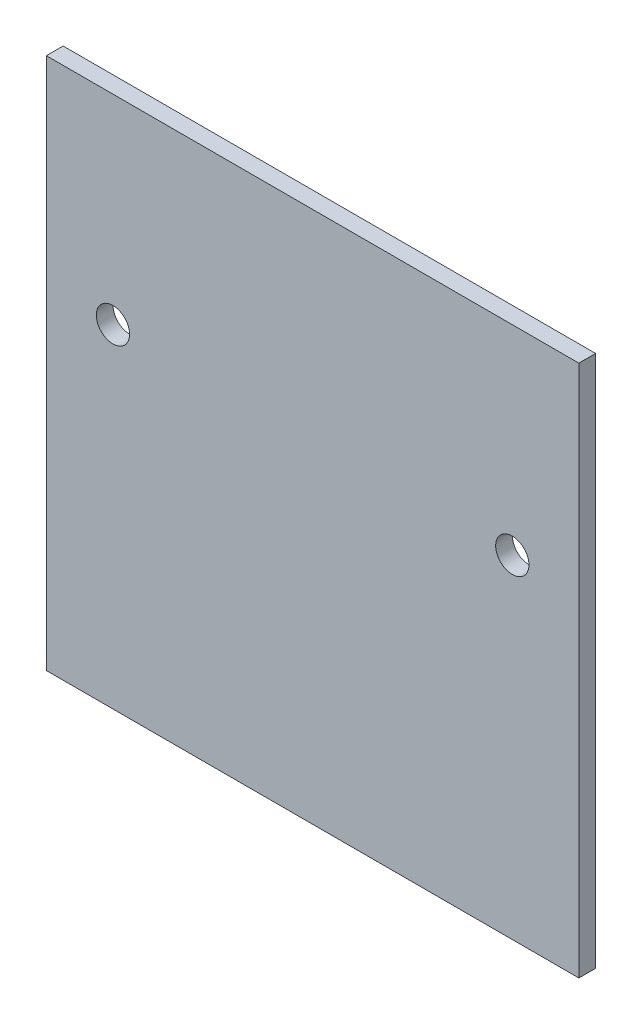
SolidWorks part; units mm, degrees
material "6061 Alloy"
ref_plane "Front Plane" through (0, 0, 0) normal (0, 0, 1) x (1, 0, 0)
ref_plane "Top Plane" through (0, 0, 0) normal (0, 1, 0) x (1, 0, 0)
ref_plane "Right Plane" through (0, 0, 0) normal (1, 0, 0) x (0, 0, -1)
sketch "Sketch2" plane through (0, 0, 0) normal (0, 0, 1) x (1, 0, 0)
  line L0 (367.9685, -43.1374) -> (375.3903, -43.1374) construction
  line L1 (339.8232, 33.108) -> (339.8232, -119.3829) construction
  line L3 (365.2232, -43.1374) -> (365.2232, -17.7374) construction
  line L4 (365.2232, -17.7374) -> (339.8232, -17.7374)
  line L5 (365.2232, -17.7374) -> (365.2232, -68.5374)
  line L6 (314.4232, -17.7374) -> (339.8232, -17.7374)
  line L7 (314.4232, -17.7374) -> (314.4232, -68.5374)
  line L8 (365.2232, -68.5374) -> (339.8237, -68.5374)
  line L9 (314.4232, -68.5374) -> (339.8237, -68.5374)
  line L10 (390.6232, 33.108) -> (289.0232, 33.108)
  line L11 (289.0232, 33.108) -> (289.0232, -119.3829)
  line L12 (289.0232, -119.3829) -> (390.6232, -119.3829)
  line L13 (390.6232, 33.108) -> (390.6232, -119.3829)
  line L14 (289.0232, -43.1374) -> (302.835, -43.1374) construction
  line L15 (302.835, -43.1374) -> (302.835, -32.805) construction
  line L16 (302.835, -32.805) -> (367.9685, -5.8258) construction
  line L17 (367.9685, -5.8258) -> (367.9685, -43.1374) construction
  line L18 (368.6791, -6.2758) -> (368.6791, -5.8258) construction
  circle A0 centre (302.835, -32.805) radius 0.45
  circle A1 centre (367.9685, -5.8258) radius 0.45
  circle A2 centre (302.835, -53.4699) radius 0.45
  circle A3 centre (375.3903, -43.1374) radius 0.45
  circle A4 centre (367.9685, -80.449) radius 0.45
  point P28 (314.4232, -43.1374)
  dimension "D1" = 50.8
  dimension "D2" = 50.8
  dimension "D3" = 50.8
  dimension "D4" = 50.8
  dimension "D5" = 13.8118
  dimension "D6" = 50.8
  dimension "D7" = 0
  dimension "D8" = 50.8
extrude "Boss-Extrude1" add sketch "Sketch2" along normal blind 3.2
sketch "Sketch3" plane through (0, 0, 3.2) normal (0, 0, 1) x (1, 0, 0)
  line L0 (339.8232, 33.108) -> (339.8232, -119.3829) construction
  line L1 (390.6232, 33.108) -> (289.0232, 33.108) construction
  line L2 (289.0232, -119.3829) -> (390.6232, -119.3829) construction
  line L3 (289.0232, -43.1374) -> (390.6232, -43.1374) construction
  line L4 (289.0232, 33.108) -> (289.0232, -119.3829) construction
  line L5 (390.6232, -119.3829) -> (390.6232, 33.108) construction
  line L6 (390.6232, 33.108) -> (377.9232, 33.108) construction
  line L7 (377.9232, 33.108) -> (377.9232, 20.408) construction
  circle A0 centre (377.9232, 20.408) radius 3.175
  circle A1 centre (301.7232, 20.408) radius 3.175
  circle A2 centre (301.7232, -106.6829) radius 3.175
  circle A3 centre (377.9232, -106.6829) radius 3.175
  dimension "D1" = 12.7
  dimension "D2" = 12.7
extrude "Cut-Extrude1" cut sketch "Sketch3" against normal blind 10
sketch "Sketch4" [suppressed] plane through (0, 0, 3.2) normal (0, 0, 1) x (1, 0, 0)
  line L0 (314.4232, -17.7374) -> (314.4232, -68.5374)
  line L1 (314.4232, -17.7374) -> (314.4232, -68.5374) construction
  line L2 (314.4232, -17.7374) -> (365.2232, -17.7374)
  line L3 (365.2232, -17.7374) -> (365.2232, -68.5374)
  line L4 (365.2232, -68.5374) -> (314.4232, -68.5374)
extrude "Boss-Extrude2" [suppressed] add sketch "Sketch4" against normal up to surface (3.2 mm away) up to face at (374.7482, -106.6829, 0)
sketch "Sketch5" plane through (0, 0, 3.2) normal (0, 0, 1) x (1, 0, 0)
  line L0 (289.0232, -43.1374) -> (390.6232, -43.1374) construction
  line L1 (289.0232, 33.108) -> (289.0232, -119.3829) construction
  line L2 (390.6232, -119.3829) -> (390.6232, 33.108) construction
  line L3 (390.6232, -43.1374) -> (390.6232, 7.6626)
  line L4 (390.6232, 7.6626) -> (289.0232, 7.6626)
  line L5 (289.0232, 7.6626) -> (289.0232, -43.1374)
  line L6 (289.0232, -43.1374) -> (289.0232, -93.9374)
  line L7 (289.0232, -93.9374) -> (390.6232, -93.9374)
  line L8 (390.6232, -93.9374) -> (390.6232, -43.1374)
  dimension "D1" = 50.8
  dimension "D2" = 50.8
extrude "Cut-Extrude3" cut sketch "Sketch5" against normal through all flip side to cut
sketch "Sketch6" plane through (0, 0, 3.2) normal (0, 0, 1) x (1, 0, 0)
  line L0 (298.5822, 7.6626) -> (298.5822, -87.2182)
  line L1 (298.5822, -87.2182) -> (383.0381, -87.2182)
  line L2 (383.0381, -87.2182) -> (383.0381, 7.6626)
  line L3 (383.0381, 7.6626) -> (298.5822, 7.6626)
  line L4 (390.6232, 7.6626) -> (289.0232, 7.6626) construction
extrude "Boss-Extrude3" add sketch "Sketch6" against normal up to surface (3.2 mm away) up to face at (339.8232, -43.1374, 0)
sketch "Sketch7" plane through (0, 0, 3.2) normal (0, 0, 1) x (1, 0, 0)
  line L0 (298.5482, -30.4374) -> (301.7232, -30.4374) construction
  line L2 (339.8232, 7.6626) -> (339.8232, -93.9374) construction
  line L3 (390.6232, 7.6626) -> (289.0232, 7.6626) construction
  line L4 (289.0232, -93.9374) -> (390.6232, -93.9374) construction
  circle A0 centre (301.7232, -30.4374) radius 3.175
  circle A1 centre (377.9232, -30.4374) radius 3.175
  dimension "D1" = 38.1
extrude "Cut-Extrude4" cut sketch "Sketch7" against normal blind 10
sketch "Sketch8" [suppressed] plane through (0, 0, 3.2) normal (0, 0, 1) x (1, 0, 0)
  line L0 (295.4324, 2.9788) -> (295.4324, -85.513)
  line L1 (295.4324, -85.513) -> (384.8396, -85.513)
  line L2 (384.8396, -85.513) -> (384.8396, 2.9788)
  line L3 (384.8396, 2.9788) -> (295.4324, 2.9788)
extrude "Boss-Extrude4" [suppressed] add sketch "Sketch8" against normal up to surface (3.2 mm away) up to face at (374.7482, -30.4374, 0)
sketch "Sketch9" [suppressed] plane through (0, 0, 3.2) normal (0, 0, 1) x (1, 0, 0)
  line L2 (289.0232, 33.108) -> (289.0232, -119.3829) construction
  line L3 (289.0232, -17.7829) -> (390.6232, -17.7829)
  line L4 (390.6232, -119.3829) -> (390.6232, 33.108) construction
  line L5 (390.6232, -17.7829) -> (390.6232, 33.108)
  line L6 (390.6232, 33.108) -> (289.0232, 33.108)
  line L7 (289.0232, 33.108) -> (289.0232, -17.7829)
extrude "Cut-Extrude5" [suppressed] cut sketch "Sketch9" against normal blind 152.4
sketch "Sketch10" plane through (0, 0, 3.2) normal (0, 0, 1) x (1, 0, 0)
  line L2 (301.7232, -113.0329) -> (390.6232, -113.0329)
  line L3 (390.6232, -93.9374) -> (390.6232, 7.6626) construction
  line L4 (390.6232, -113.0329) -> (390.6232, -119.3829)
  line L5 (390.6232, -119.3829) -> (289.0232, -119.3829)
  line L6 (289.0232, -119.3829) -> (289.0232, -113.0329)
  line L7 (289.0232, 7.6626) -> (289.0232, -93.9374) construction
  line L8 (289.0232, -113.0329) -> (301.7232, -113.0329)
extrude "Cut-Extrude6" [suppressed] cut sketch "Sketch10" against normal blind 152.4
